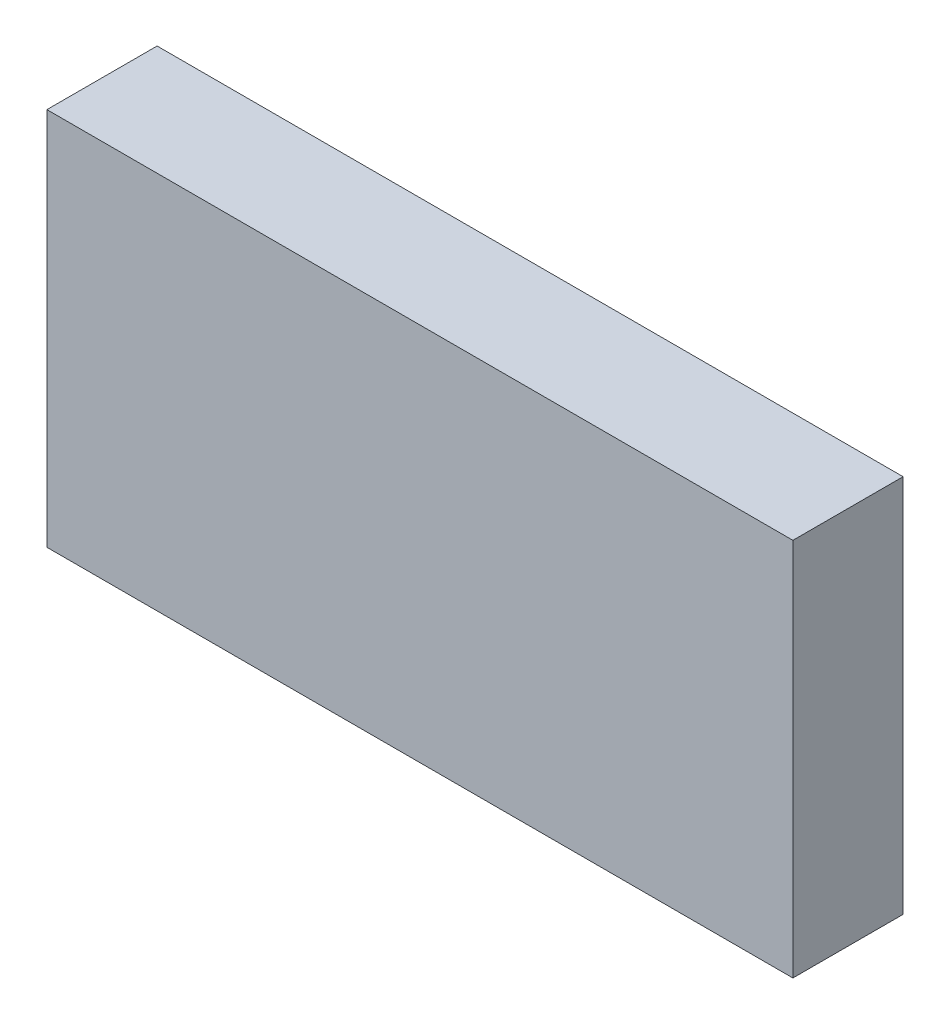
SolidWorks part; units mm, degrees
ref_plane "Front Plane" through (0, 0, 0) normal (0, 0, 1) x (1, 0, 0)
ref_plane "Top Plane" through (0, 0, 0) normal (0, 1, 0) x (1, 0, 0)
ref_plane "Right Plane" through (0, 0, 0) normal (1, 0, 0) x (0, 0, -1)
sketch "Sketch2" plane through (0, 0, 0) normal (0, 1, 0) x (1, 0, 0)
  line L1 (-338.5, 50) -> (338.5, 50)
  line L2 (-338.5, 50) -> (-338.5, -50)
  line L3 (-338.5, -50) -> (338.5, -50)
  line L4 (338.5, 50) -> (338.5, -50)
  line L5 (-338.5, 50) -> (338.5, -50) construction
  line L6 (-338.5, -50) -> (338.5, 50) construction
  point P0 (0, 0)
  dimension "D1" = 677
  dimension "D2" = 100
extrude "Boss-Extrude1" add sketch "Sketch2" along normal blind 172 and the other way blind 172 contours L1 L4 L3 L2
ref_plane "Plane3" through (118.75, 0, 0) normal (1, 0, 0) x (0, 0, -1)
ref_plane "Plane4" through (-118.75, 0, 0) normal (1, 0, 0) x (0, 0, -1)
ref_axis "Axis3" through (118.75, 272.0533, 0) along (0, -1, 0)
ref_axis "Axis4" through (-118.75, 277.5009, 0) along (0, -1, 0)
